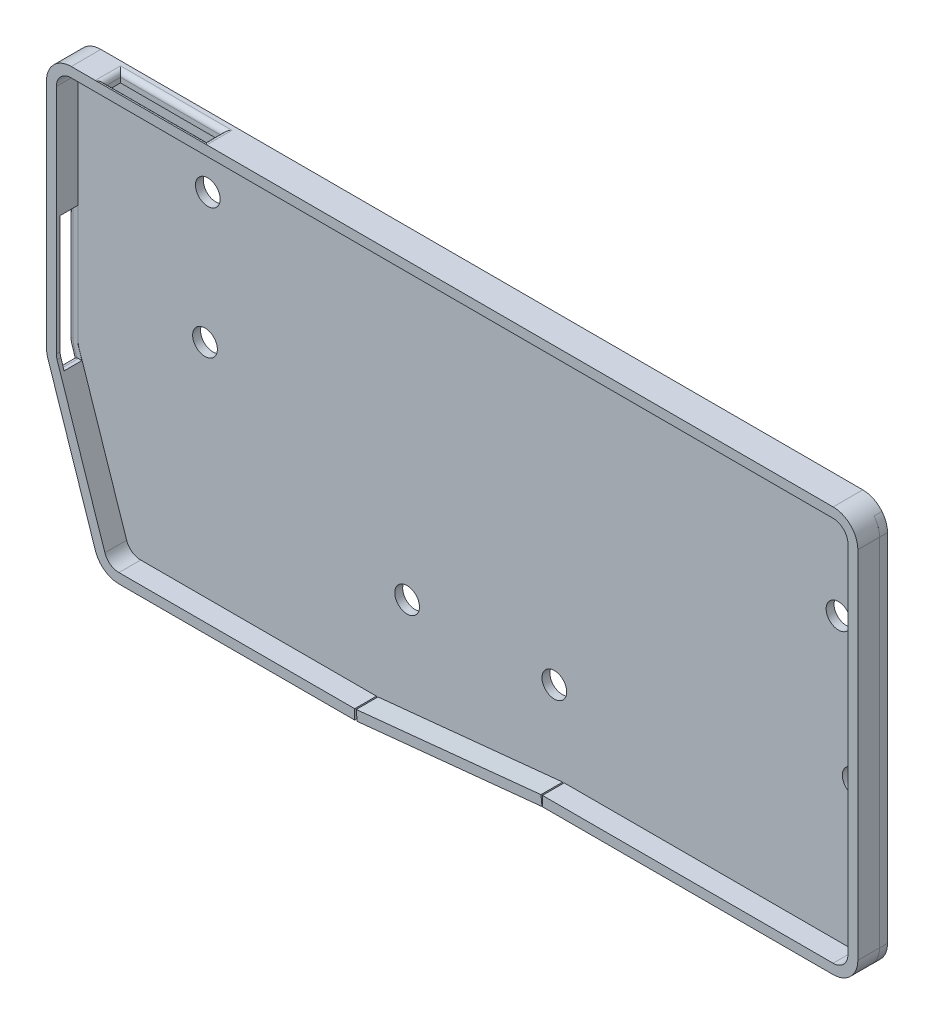
SolidWorks part; units mm, degrees
ref_plane "Front Plane" through (0, 0, 0) normal (0, 0, 1) x (1, 0, 0)
ref_plane "Top Plane" through (0, 0, 0) normal (0, 1, 0) x (1, 0, 0)
ref_plane "Right Plane" through (0, 0, 0) normal (1, 0, 0) x (0, 0, -1)
sketch "Sketch1" plane through (0, 0, 0) normal (0, 0, 1) x (1, 0, 0)
  line B0 (-90.6145, 42.2214) -> (63.6355, 42.1251)
  arc B1 (-90.6145, 42.2214) -> (-95.6176, 37.2214) centre (-90.6176, 37.2214) ccw
  arc B2 (-90.6157, 40.2214) -> (-93.6176, 37.2214) centre (-90.6176, 37.2214) ccw
  line B3 (-90.6157, 40.2214) -> (63.6343, 40.1251)
  line B4 (-95.6176, -9.6899) -> (-95.6176, 37.2214)
  line B5 (-93.6176, -9.6899) -> (-93.6176, 37.2214)
  arc B6 (66.6324, 37.1251) -> (63.6343, 40.1251) centre (63.6324, 37.1251) ccw
  arc B7 (68.6324, 37.1251) -> (63.6355, 42.1251) centre (63.6324, 37.1251) ccw
  line B8 (68.6324, 37.1251) -> (68.6324, -34.8768)
  line B9 (66.6324, 37.1251) -> (66.6324, -34.8768)
  arc B10 (63.6324, -39.8768) -> (68.6324, -34.8768) centre (63.6324, -34.8768) ccw
  line B11 (63.6324, -39.8768) -> (4.7832, -39.8768)
  line B12 (4.6829, -39.8818) -> (-32.717, -43.6515)
  line B13 (-33.2184, -43.6768) -> (-80.9553, -43.6768)
  arc B14 (-85.6987, -40.2579) -> (-80.9553, -43.6768) centre (-80.9553, -38.6768) ccw
  line B15 (-83.8014, -39.6254) -> (-93.4637, -10.6386)
  line B16 (-85.6987, -40.2579) -> (-95.361, -11.2711)
  arc B17 (-95.6176, -9.6899) -> (-95.361, -11.2711) centre (-90.6176, -9.6899) ccw
sketch_block_instance "wall_outline-1"
sketch_block "wall_outline"
extrude "Extrude-Thin1" add sketch "Sketch1" along normal blind 6 thin contours B11 B10 B8 B7 B0 B1 B4 B17 B16 B14 B13 | B12 thin type one direction wall 2
sketch "Sketch2" plane through (0, 0, 0) normal (0, 0, 1) x (1, 0, 0)
  line B0 (-90.6095, 42.2152) -> (63.6405, 42.119)
  circle B1 centre (-67.3626, 29.6171) radius 2.5
  circle B2 centre (-67.3626, 29.6171) radius 1
  line B3 (68.6374, 37.119) -> (68.6374, -34.8829)
  circle B4 centre (-67.9326, 3.0171) radius 2.5
  line B5 (-95.6126, -9.6961) -> (-95.6126, 37.2152)
  arc B6 (-90.6095, 42.2152) -> (-95.6126, 37.2152) centre (-90.6126, 37.2152) ccw
  line B7 (-85.6938, -40.264) -> (-95.3561, -11.2772)
  line B8 (63.6374, -39.8829) -> (4.7882, -39.8829)
  arc B9 (68.6374, 37.119) -> (63.6405, 42.119) centre (63.6374, 37.119) ccw
  circle B10 centre (63.5874, -8.3829) radius 2.5
  circle B11 centre (-27.0126, -21.6829) radius 2.5
  line B12 (4.6879, -39.8879) -> (-32.712, -43.6577)
  arc B13 (63.6374, -39.8829) -> (68.6374, -34.8829) centre (63.6374, -34.8829) ccw
  arc B14 (-85.6938, -40.264) -> (-80.9504, -43.6829) centre (-80.9504, -38.6829) ccw
  line B15 (-33.2135, -43.6829) -> (-80.9504, -43.6829)
  arc B16 (4.7882, -39.8829) -> (4.6879, -39.8879) centre (4.7882, -40.8829) ccw
  arc B17 (-33.2135, -43.6829) -> (-32.712, -43.6577) centre (-33.2135, -38.6829) ccw
  arc B18 (-95.6126, -9.6961) -> (-95.3561, -11.2772) centre (-90.6126, -9.6961) ccw
  circle B19 centre (2.7874, -21.6829) radius 2.5
  circle B20 centre (60.3174, 19.1671) radius 2.5
  circle B21 centre (-67.9326, 3.0171) radius 1
  circle B22 centre (-27.0126, -21.6829) radius 1
  circle B23 centre (2.7874, -21.6829) radius 1
  circle B24 centre (63.5874, -8.3829) radius 1
  circle B25 centre (60.3174, 19.1671) radius 1
sketch_block_instance "xlBoard-1"
sketch_block "xlBoard"
extrude "Boss-Extrude3" add sketch "Sketch2" along normal blind 1.6 contours B0 B6 B5 B18 B7 B14 B15 B17 B12 B16 B8 B13 B3 B9 B20 B10 B19 B11 B4 B1 region at (-13.4565, 0.6202, 0)
sketch "Sketch6" plane through (0.0263, 42.1648, 0) normal (0.0006, 1, 0) x (1, -0.0006, 0)
  line L1 (-84.7673, -1.8905) -> (-64.1998, -1.8905)
  line L2 (-84.7673, -1.8905) -> (-84.7673, -5.0715)
  line L3 (-84.7673, -5.0715) -> (-64.1998, -5.0715)
  line L4 (-64.1998, -1.8905) -> (-64.1998, -5.0715)
extrude "Cut-Extrude3" cut sketch "Sketch6" against normal blind 4
fillet "Fillet1" radius 1 4 edges at (-64.1734, 42.2049, 3.481) (-74.4572, 42.2113, 5.0715) (-84.741, 42.2177, 3.481) (-74.4572, 42.2113, 1.8905)
sketch "Sketch7" plane through (-95.6176, 0, 0) normal (-1, 0, 0) x (0, 0, 1)
  line L1 (1.6385, 14.2009) -> (5.2428, 14.2009)
  line L2 (1.6385, 14.2009) -> (1.6385, -12.6136)
  line L3 (1.6385, -12.6136) -> (5.2428, -12.6136)
  line L4 (5.2428, 14.2009) -> (5.2428, -12.6136)
extrude "Cut-Extrude6" cut sketch "Sketch7" against normal blind 4
fillet "Fillet3" radius 1 7 edges at (-95.1373, -11.9423, 5.2428) (-95.553, -10.4908, 5.2428) (-95.1373, -11.9423, 1.6385) (-95.553, -10.4908, 1.6385) (-95.6176, 2.2555, 5.2428) (-95.6176, 14.2009, 3.4406) (-95.6176, 2.2555, 1.6385)
fillet "Fillet4" radius 1 1 edges at (-94.9135, -12.6136, 3.3192)
